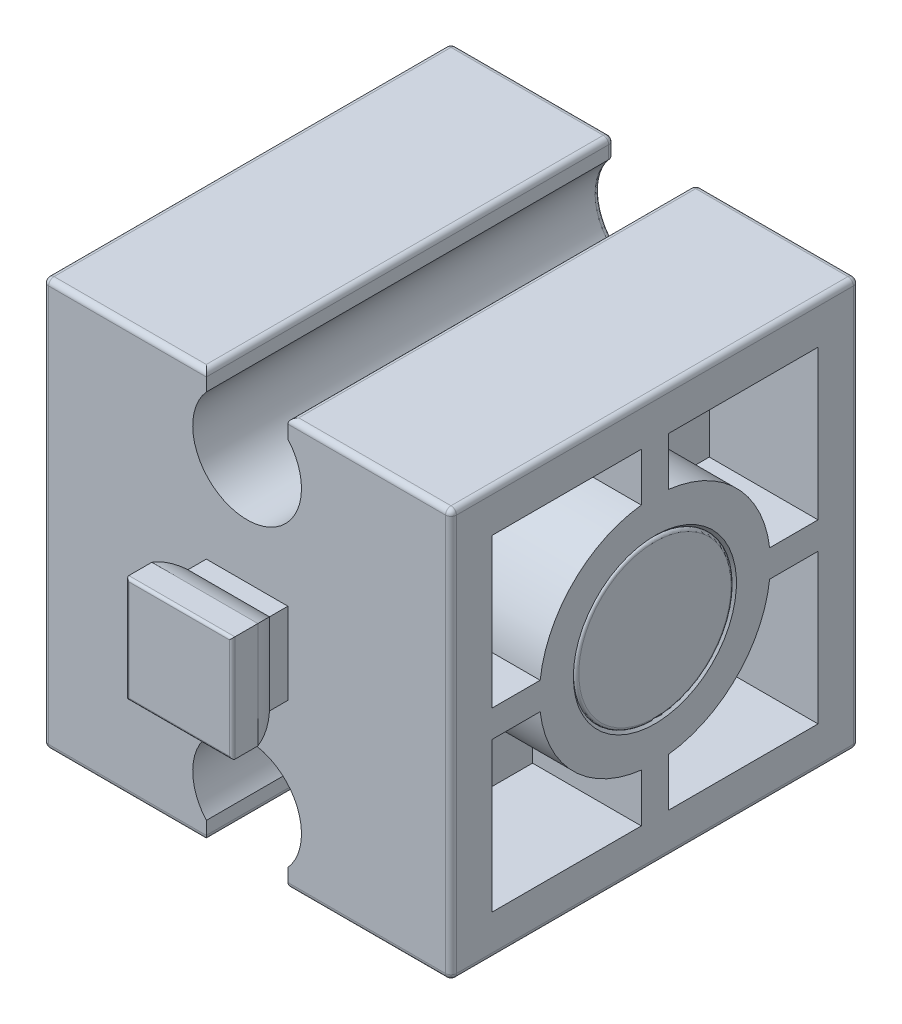
SolidWorks part; units mm, degrees
ref_plane "前视基准面" through (0, 0, 0) normal (0, 0, 1) x (1, 0, 0)
ref_plane "上视基准面" through (0, 0, 0) normal (0, 1, 0) x (1, 0, 0)
ref_plane "右视基准面" through (0, 0, 0) normal (1, 0, 0) x (0, 0, -1)
sketch "草图1" plane through (0, 0, 0) normal (0, 0, 1) x (1, 0, 0)
  line L1 (-7.5, -7.5) -> (7.5, -7.5)
  line L2 (-7.5, -7.5) -> (-7.5, 7.5)
  line L3 (-7.5, 7.5) -> (7.5, 7.5)
  line L4 (7.5, -7.5) -> (7.5, 7.5)
extrude "凸台-拉伸1" add sketch "草图1" against normal blind 15
sketch "草图2" plane through (0, 0, 0) normal (0, 0, 1) x (1, 0, 0)
  line L1 (-1.5, -1.5) -> (1.5, -1.5)
  line L2 (-1.5, -1.5) -> (-1.5, 1.5)
  line L3 (-1.5, 1.5) -> (1.5, 1.5)
  line L4 (1.5, -1.5) -> (1.5, 1.5)
extrude "凸台-拉伸2" add sketch "草图2" along normal blind 1
sketch "草图3" plane through (0, 0, 0) normal (1, 0, 0) x (0, 0, -1)
  line L0 (-2.5, 1.95) -> (-2.5, -1.95)
  line L1 (-2.5, 1.95) -> (-1.5556, 1.95)
  line L2 (-2.5, -1.95) -> (-1.5556, -1.95)
  line L3 (-0.6771, 1.5) -> (-0.6771, -1.5)
  arc A0 (-1.5556, -1.95) -> (-0.6771, -1.5) centre (-2, 0) ccw
  arc A1 (-0.6771, 1.5) -> (-1.5556, 1.95) centre (-2, 0) ccw
extrude "凸台-拉伸3" add sketch "草图3" along normal blind 4 and the other way blind 4 separate body
sketch "草图4" plane through (0, 0, 0) normal (0, 1, 0) x (1, 0, 0)
  line L0 (-4, -2.5) -> (-1.95, -2.5)
  line L1 (-1.95, -2.5) -> (-1.95, -1.5556)
  line L2 (1.95, -2.5) -> (1.95, -1.5556)
  line L3 (-4, -2.5) -> (-4, -0.6771)
  line L4 (-1.5, -0.6771) -> (-4, -0.6771)
  line L5 (4, -0.6771) -> (4, -2.5)
  line L7 (1.95, -2.5) -> (4, -2.5)
  line L8 (-4, -0.6771) -> (4, -0.6771) construction
  line L12 (1.5, -0.6771) -> (4, -0.6771)
  arc A0 (-1.5, -0.6771) -> (-1.95, -1.5556) centre (0, -2) ccw
  arc A1 (1.95, -1.5556) -> (1.5, -0.6771) centre (0, -2) ccw
extrude "切除-拉伸1" cut sketch "草图4" against normal up to next (1.95 mm away) and the other way up to next (1.95 mm away)
sketch "草图5" plane through (-7.5, 0, 0) normal (-1, 0, 0) x (0, 0, 1)
  circle A0 centre (-7.5, 0) radius 2
extrude "切除-拉伸2" cut sketch "草图5" against normal blind 10
sketch "草图6" plane through (-7.5, 0, 0) normal (-1, 0, 0) x (0, 0, 1)
  line L0 (-8, 6.5) -> (-8, 2.958)
  line L1 (-14, -6.5) -> (-8, -6.5)
  line L2 (-14, -6.5) -> (-14, -0.5)
  line L3 (-14, 6.5) -> (-8, 6.5)
  line L4 (-1, -6.5) -> (-1, -0.5)
  line L5 (-7, 6.5) -> (-7, 2.958)
  line L6 (-14, 0.5) -> (-10.458, 0.5)
  line L7 (-14, -0.5) -> (-10.458, -0.5)
  line L8 (-8, -2.958) -> (-8, -6.5)
  line L9 (-4.542, 0.5) -> (-1, 0.5)
  line L10 (-4.542, -0.5) -> (-1, -0.5)
  line L11 (-7, -2.958) -> (-7, -6.5)
  line L12 (-7, 6.5) -> (-1, 6.5)
  line L13 (-14, 0.5) -> (-14, 6.5)
  line L14 (-7, -6.5) -> (-1, -6.5)
  line L15 (-1, 0.5) -> (-1, 6.5)
  arc A0 (-7, -2.958) -> (-4.542, -0.5) centre (-7.5, 0) ccw
  arc A1 (-10.458, -0.5) -> (-8, -2.958) centre (-7.5, 0) ccw
  arc A2 (-8, 2.958) -> (-10.458, 0.5) centre (-7.5, 0) ccw
  arc A3 (-4.542, 0.5) -> (-7, 2.958) centre (-7.5, 0) ccw
extrude "切除-拉伸3" cut sketch "草图6" against normal blind 4
sketch "草图7" plane through (0, 0, 0) normal (0, 0, 1) x (1, 0, 0)
  line L0 (-1.5, -7.5) -> (-1.5, -6.8229)
  line L1 (-7.5, -7.5) -> (7.5, -7.5) construction
  line L2 (1.5, -7.5) -> (1.5, -6.8229)
  line L3 (-1.5, 7.5) -> (1.5, 7.5)
  line L5 (1.5, 7.5) -> (1.5, 6.8229)
  line L6 (-1.5, 7.5) -> (-1.5, 6.8229)
  line L7 (-1.5, -7.5) -> (1.5, -7.5)
  arc A0 (1.5, -6.8229) -> (-1.5, -6.8229) centre (0, -5.5) ccw
  arc A1 (-1.5, 6.8229) -> (1.5, 6.8229) centre (0, 5.5) ccw
extrude "切除-拉伸5" cut sketch "草图7" against normal through all
fillet "圆角1" radius 0.1 4 edges at (1.95, 0, 2.5) (0, -1.95, 2.5) (-1.95, 0, 2.5) (0, 1.95, 2.5)
fillet "圆角2" radius 0.2 26 edges at (0, -3.5, -15) (1.5, -7.1614, -15) (4.5, -7.5, -15) (7.5, 0, -15) (4.5, 7.5, -15) (1.5, 7.1614, -15) (0, 3.5, -15) (-1.5, 7.1614, -15) (-4.5, 7.5, -15) (-7.5, 0, -15) (-4.5, -7.5, -15) (-1.5, -7.1614, -15) (-7.5, 0, 0) (-4.5, 7.5, 0) (4.5, 7.5, 0) (7.5, 0, 0) (4.5, -7.5, 0) (-4.5, -7.5, 0) (7.5, 7.5, -7.5) (1.5, 7.5, -7.5) (-7.5, 7.5, -7.5) (-1.5, 7.5, -7.5) (7.5, -7.5, -7.5) (1.5, -7.5, -7.5) (-7.5, -7.5, -7.5) (-1.5, -7.5, -7.5)
ref_plane "基准面1" through (0, 0, -7.5) normal (0, 0, 1) x (1, 0, 0)
mirror "镜向2" about plane through (0, 0, -7.5) normal (0, 0, 1) of "凸台-拉伸3", "切除-拉伸1", "圆角1", "凸台-拉伸2"
sketch "草图8" plane through (7.5, 0, 0) normal (1, 0, 0) x (0, 0, -1)
  line L0 (0, 0) -> (7.5, 0) construction
  line L1 (13.5, 6) -> (13.5, 0.5)
  line L2 (13.5, 6) -> (8, 6)
  line L3 (13.5, -6) -> (8, -6)
  line L4 (1.5, 6) -> (1.5, 0.5)
  line L5 (13.5, 6) -> (1.5, -6) construction
  line L6 (13.5, -6) -> (1.5, 6) construction
  line L7 (7.5, 0) -> (7.5, 6) construction
  line L8 (11.7205, 0.5) -> (13.5, 0.5)
  line L9 (11.7205, -0.5) -> (13.5, -0.5)
  line L10 (7, 4.2205) -> (7, 6)
  line L11 (8, 4.2205) -> (8, 6)
  line L12 (8, -4.2205) -> (8, -6)
  line L13 (7, -4.2205) -> (7, -6)
  line L14 (3.2795, -0.5) -> (1.5, -0.5)
  line L15 (3.2795, 0.5) -> (1.5, 0.5)
  line L16 (13.5, -0.5) -> (13.5, -6)
  line L17 (7, -6) -> (1.5, -6)
  line L18 (1.5, -0.5) -> (1.5, -6)
  line L19 (7, 6) -> (1.5, 6)
  arc A0 (7, 4.2205) -> (3.2795, 0.5) centre (7.5, 0) ccw
  arc A1 (3.2795, -0.5) -> (7, -4.2205) centre (7.5, 0) ccw
  arc A2 (8, -4.2205) -> (11.7205, -0.5) centre (7.5, 0) ccw
  arc A3 (11.7205, 0.5) -> (8, 4.2205) centre (7.5, 0) ccw
  point P4 (8, 0)
  point P11 (7, 0)
  point P29 (7.5, 0)
  dimension "D2" = 8.5
  dimension "D1" = 7.5
  dimension "D3" = 12
extrude "切除-拉伸6" cut sketch "草图8" against normal blind 4
sketch "草图9" plane through (0, 0, 0) normal (0, 1, 0) x (1, 0, 0)
  line L0 (0, 0) -> (0, 7.5) construction
  line L1 (0, 7.5) -> (7.5, 7.5) construction
  line L2 (7.5, 14.8) -> (7.5, 0.2) construction
  line L3 (7.5, 7.5) -> (7.5, 10.4) construction
  line L4 (7.5, 10.4) -> (7.4, 10.4)
  line L5 (7.4, 10.4) -> (7.5, 10.5)
  line L6 (7.5, 10.5) -> (7.5, 10.4)
  dimension "D1" = 7.5
  dimension "D2" = 2.9
  dimension "D3" = 0.1
  dimension "D4" = 0.1
revolve "切除-旋转1" cut sketch "草图9" angle 360 about L1
fillet "圆角3" radius 0.1 1 edges at (7.5, 0, -4.6)
